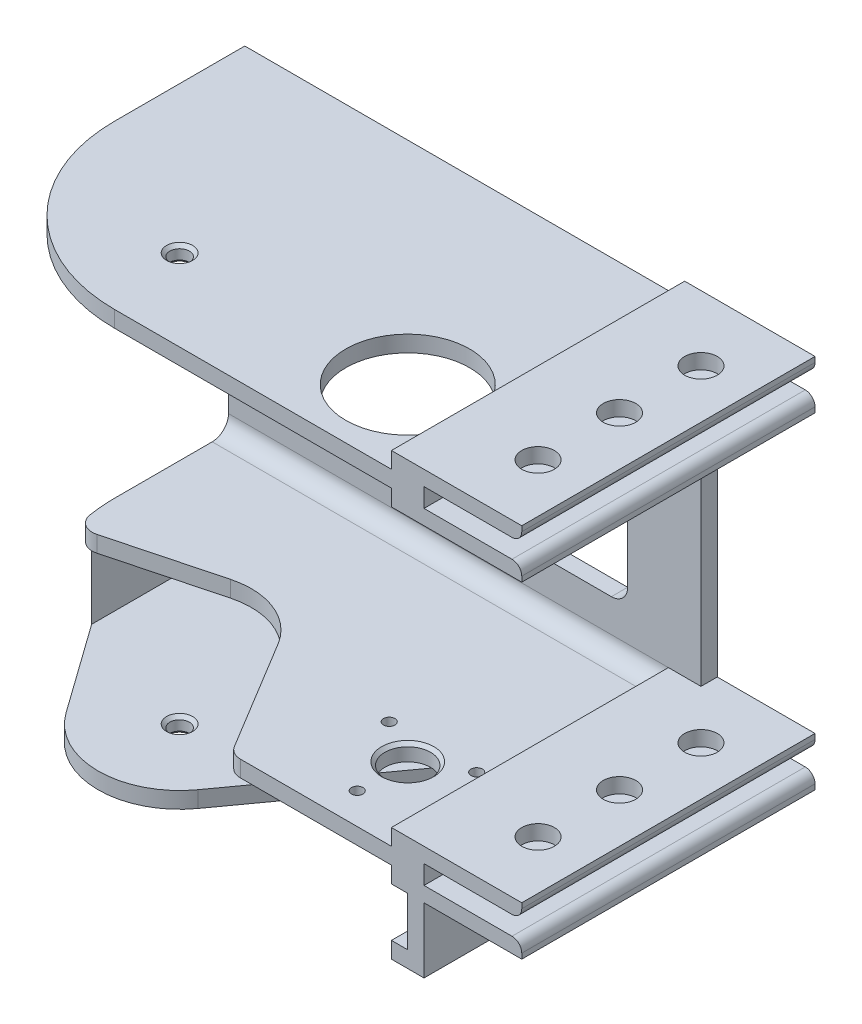
SolidWorks part; units mm, degrees
ref_plane "정면" through (0, 0, 0) normal (0, 0, 1) x (1, 0, 0)
ref_plane "윗면" through (0, 0, 0) normal (0, 1, 0) x (1, 0, 0)
ref_plane "우측면" through (0, 0, 0) normal (1, 0, 0) x (0, 0, -1)
sketch "스케치1" plane through (0, 0, 0) normal (0, 0, 1) x (1, 0, 0)
  line L0 (67.5, -47.6) -> (-67.5, -47.6)
  line L1 (-67.5, -52.6) -> (67.5, -52.6)
  line L2 (-67.5, -52.6) -> (-67.5, -72.6)
  line L3 (-67.5, -72.6) -> (67.5, -72.6)
  line L4 (67.5, -77.6) -> (-67.5, -77.6)
  line L5 (-52.5, -47.6) -> (-12.5, -47.6)
  line L6 (67.5, -57.6) -> (67.5, -72.6)
  line L7 (67.5, -47.6) -> (72.5, -47.6)
  line L8 (72.5, -47.6) -> (72.5, -52.6)
  line L9 (72.5, -57.6) -> (72.5, -77.6)
  line L10 (72.5, -77.6) -> (67.5, -77.6)
  line L11 (-67.5, -47.6) -> (-72.5, -47.6)
  line L12 (-72.5, -47.6) -> (-72.5, -77.6)
  line L13 (-72.5, -77.6) -> (-67.5, -77.6)
  line L14 (-72.5, 47.6) -> (72.5, 47.6)
  line L15 (-72.5, -47.6) -> (-72.5, 47.6)
  line L16 (72.5, -42.6) -> (72.5, 42.6)
  line L17 (72.5, 47.6) -> (72.5, 52.6)
  line L18 (72.5, 52.6) -> (-72.5, 52.6)
  line L19 (-72.5, 52.6) -> (-72.5, 47.6)
  line L20 (62.5, 42.6) -> (102.5, 42.6)
  line L21 (102.5, 42.6) -> (102.5, 47.6)
  line L22 (102.5, 47.6) -> (62.5, 47.6)
  line L23 (62.5, 47.6) -> (62.5, 42.6)
  line L24 (62.5, 52.6) -> (102.5, 52.6)
  line L25 (102.5, 52.6) -> (102.5, 57.6)
  line L26 (102.5, 57.6) -> (62.5, 57.6)
  line L27 (62.5, 57.6) -> (62.5, 52.6)
  line L28 (72.5, 0) -> (-72.5, 0) construction
  line L29 (62.5, -42.6) -> (102.5, -42.6)
  line L30 (102.5, -42.6) -> (102.5, -47.6)
  line L31 (102.5, -47.6) -> (62.5, -47.6)
  line L32 (62.5, -47.6) -> (62.5, -42.6)
  line L33 (62.5, -52.6) -> (102.5, -52.6)
  line L34 (102.5, -52.6) -> (102.5, -57.6)
  line L35 (102.5, -57.6) -> (62.5, -57.6)
  line L36 (62.5, -57.6) -> (62.5, -52.6)
  line L37 (0, 52.6) -> (0, -77.6) construction
extrude "보스-돌출1" add sketch "스케치1" against normal blind 5 contours L18 L19 L14 L17 | L0 L32 L29 L16 L20 L23 L14 L15 L11 | L9 L35 L6 L3 L2 L1 L33 L8 L7 L0 L11 L12 L13 L4 L10 | L35 L36 L1 L2 L3 L6 | L14 L23 L20 L21 L22 | L26 L27 L18 L24 L25 | L32 L0 L7 L31 L30 L29 | L36 L35 L34 L33 L1 region at (70, -49.0807, 0) region at (82.5, -45.1, 0) region at (-0.4926, 0, 0) region at (82.5, -55.1, 0) region at (82.5, 45.1, 0) region at (-0.6075, -62.6701, 0) region at (0, 50.1, 0) region at (82.5, 55.1, 0)
extrude "보스-돌출2" add sketch "스케치1<3>" along normal blind 85 contours L18 L19 L14 L17 | L9 L35 L6 L3 L2 L1 L33 L8 L7 L0 L11 L12 L13 L4 L10 | L36 L35 L34 L33 L1 | L32 L0 L7 L31 L30 L29 | L14 L23 L20 L21 L22 | L26 L27 L18 L24 L25 region at (70, -49.0807, 0) region at (82.5, -45.1, 0) region at (82.5, -55.1, 0) region at (82.5, 45.1, 0) region at (0, 50.1, 0) region at (82.5, 55.1, 0)
sketch "스케치1<3>" plane through (0, 0, 0) normal (0, 0, 1) x (1, 0, 0) same geometry as "스케치1"
sketch "스케치2" plane through (0, 0, 85) normal (0, 0, 1) x (1, 0, 0)
  line L0 (102.5, -42.6) -> (102.5, -47.6) construction
  line L1 (72.5, -53) -> (102.5, -53)
  line L2 (72.5, -53) -> (72.5, -47.2)
  line L3 (72.5, -47.2) -> (102.5, -47.2)
  line L4 (102.5, -53) -> (102.5, -47.2)
  line L5 (102.5, 52.6) -> (102.5, 57.6) construction
  line L6 (72.5, 47.2) -> (102.5, 47.2)
  line L7 (72.5, 47.2) -> (72.5, 53)
  line L8 (72.5, 53) -> (102.5, 53)
  line L9 (102.5, 47.2) -> (102.5, 53)
  line L10 (102.5, 52.6) -> (72.5, 52.6) construction
  line L11 (72.5, 47.6) -> (102.5, 47.6) construction
  line L12 (102.5, -47.6) -> (72.5, -47.6) construction
  line L13 (72.5, -52.6) -> (102.5, -52.6) construction
  line L14 (72.5, -47.6) -> (72.5, -52.6) construction
  line L15 (72.5, 47.6) -> (72.5, 52.6) construction
  dimension "D1" = 0.4
  dimension "D2" = 0.4
  dimension "D3" = 0.4
  dimension "D4" = 0.4
extrude "컷-돌출1" cut sketch "스케치2" against normal blind 130
sketch "스케치3" plane through (0, -77.6, 0) normal (0, -1, 0) x (1, 0, 0)
  line L0 (-72.5, 60) -> (72.5, 60) construction
  line L1 (-72.5, -5) -> (-72.5, 85) construction
  line L2 (72.5, -5) -> (72.5, 85) construction
  line L3 (42.5, 85) -> (42.5, -5) construction
  line L4 (-72.5, 85) -> (72.5, 85) construction
  line L5 (-72.5, -5) -> (72.5, -5) construction
  line L6 (-27.5, -5) -> (-27.5, 85) construction
  circle A0 centre (-27.5, 60) radius 3
  circle A1 centre (42.5, 60) radius 3
  dimension "D1" = 65
  dimension "D4" = 6
  dimension "D5" = 6
  dimension "D2" = 45
  dimension "D3" = 70
extrude "컷-돌출2" cut sketch "스케치3" against normal blind 188
sketch "스케치4" plane through (0, -47.6, 0) normal (0, 1, 0) x (1, 0, 0)
  circle A0 centre (-27.5, -60) radius 22
  dimension "D1" = 44
extrude "컷-돌출3" cut sketch "스케치4" against normal blind 10
sketch "스케치5" plane through (0, -77.6, 0) normal (0, -1, 0) x (1, 0, 0)
  line L0 (42.5, 60) -> (42.5, -5) construction
  line L1 (-72.5, -5) -> (72.5, -5) construction
  line L2 (42.5, 40) -> (42.5, 143.4031) construction
  line L3 (22.5, 40) -> (22.5, 143.4031)
  line L4 (62.5, 40) -> (62.5, 143.4031)
  arc A0 (22.5, 40) -> (62.5, 40) centre (42.5, 40) ccw
  arc A1 (62.5, 143.4031) -> (22.5, 143.4031) centre (42.5, 143.4031) ccw
  point P7 (42.5, 91.7016)
  dimension "D1" = 20
  dimension "D2" = 20
extrude "컷-돌출4" cut sketch "스케치5" against normal blind 10
sketch "스케치6" plane through (0, -52.6, 0) normal (0, -1, 0) x (1, 0, 0)
  circle A0 centre (42.5, 60) radius 7
  circle A1 centre (42.5, 60) radius 15.5 construction
  circle A2 centre (42.5, 75.5) radius 1.75
  circle A3 centre (55.9234, 52.25) radius 1.75
  circle A4 centre (29.0766, 52.25) radius 1.75
  point P12 (42.5, 60)
  dimension "D1" = 14
  dimension "D2" = 31
  dimension "D3" = 3.5
  dimension "D4" = 3
extrude "컷-돌출5" cut sketch "스케치6" against normal blind 10
sketch "스케치7" plane through (0, -52.6, 0) normal (0, -1, 0) x (1, 0, 0)
  circle A0 centre (42.5, 75.5) radius 3.5
  circle A1 centre (29.0766, 52.25) radius 3.5
  circle A2 centre (55.9234, 52.25) radius 3.5
  dimension "D1" = 7
extrude "컷-돌출6" cut sketch "스케치7" against normal blind 1.5
sketch "스케치8" plane through (0, -77.6, 0) normal (0, -1, 0) x (1, 0, 0)
  line L0 (-72.5, 85) -> (22.5, 85) construction
  line L1 (-7.2427, 74.6506) -> (26.2941, 28.2795)
  line L2 (-72.5, 40) -> (-47.8457, 74.5277)
  line L9 (22.5, 40) -> (22.5, 85)
  line L10 (22.5, 85) -> (-72.5, 85)
  line L11 (-72.5, 85) -> (-72.5, -5)
  line L12 (-72.5, -5) -> (72.5, -5)
  line L13 (72.5, -5) -> (72.5, 85)
  line L14 (72.5, 85) -> (62.5, 85)
  line L15 (62.5, 85) -> (62.5, 40)
  line L16 (22.5, 40) -> (22.5, 85)
  line L17 (22.5, 85) -> (-72.5, 85)
  line L18 (-72.5, 85) -> (-72.5, -5)
  line L19 (-72.5, -5) -> (72.5, -5)
  line L20 (72.5, -5) -> (72.5, 85)
  line L21 (72.5, 85) -> (62.5, 85)
  line L22 (62.5, 85) -> (62.5, 40)
  circle A0 centre (-27.5, 60) radius 25
  arc A2 (22.5, 40) -> (62.5, 40) centre (42.5, 40) ccw
  arc A3 (22.5, 40) -> (62.5, 40) centre (42.5, 40) ccw
  line M11 (22.5, 40) -> (22.5, 85)
  line M12 (22.5, 85) -> (-72.5, 85)
  line M13 (-72.5, 85) -> (-72.5, -5)
  arc M18 (62.5, 40) -> (22.5, 40) centre (42.5, 40) cw
  dimension "D1" = 0
extrude "컷-돌출7" cut sketch "스케치8" against normal up to surface (25 mm away) contours A0 L17 L2 M13 | A0 L1 M18 M11 M12 region at (9.5144, -77.6, 68.0615) region at (-61.0474, -77.6, 70.422) up to face at (42.5, -52.6, 72)
fillet "필렛2" radius 50 2 edges at (-72.5, -50.1, 85) (-72.5, 50.1, 85)
fillet "필렛3" radius 30 1 edges at (-72.2063, -65.1, 40.4113)
sketch "스케치9" plane through (0, 52.6, 0) normal (0, 1, 0) x (1, 0, 0)
  circle A0 centre (42.5, -60) radius 19
  dimension "D1" = 38
extrude "컷-돌출8" cut sketch "스케치9" against normal blind 9.5
fillet "필렛4" radius 3 4 edges at (102.5, 53, 40) (102.5, 47.2, 40) (102.5, -47.2, 40) (102.5, -53, 40)
sketch "스케치10" plane through (0, 0, 0) normal (0, 0, 1) x (1, 0, 0)
  line L0 (-72.5, -52.6) -> (-22.5, -52.6) construction
  line L1 (-50, 32.5) -> (50, 32.5)
  line L2 (-50, 32.5) -> (-50, -32.5)
  line L3 (-50, -32.5) -> (50, -32.5)
  line L4 (50, 32.5) -> (50, -32.5)
  line L5 (-50, 32.5) -> (50, -32.5) construction
  line L6 (-50, -32.5) -> (50, 32.5) construction
  line L7 (-50, -68.6) -> (50, -68.6)
  line L8 (-50, -68.6) -> (-50, -58.6)
  line L9 (-50, -58.6) -> (50, -58.6)
  line L10 (50, -68.6) -> (50, -58.6)
  line L11 (-50, -68.6) -> (50, -58.6) construction
  line L12 (-50, -58.6) -> (50, -68.6) construction
  point P0 (0, 0)
  point P6 (0, -63.6)
  dimension "D1" = 100
  dimension "D2" = 65
  dimension "D3" = 100
  dimension "D4" = 10
  dimension "D5" = 6
extrude "컷-돌출9" cut sketch "스케치10" against normal blind 9.5
sketch "스케치11" plane through (0, -47.6, 0) normal (0, 1, 0) x (1, 0, 0)
  line L0 (-33.1052, -38.726) -> (-70.6125, -48.6084)
  line L1 (-8.679, -48.6084) -> (13.3474, -85)
  line L2 (-22.5, -85) -> (62.5, -85) construction
  line L7 (-72.5, 0) -> (-72.5, -35)
  line L8 (-22.5, -85) -> (62.5, -85)
  line L9 (62.5, -85) -> (62.5, 0)
  line L10 (62.5, 0) -> (-72.5, 0)
  line L11 (-72.5, 0) -> (-72.5, -35)
  line L12 (-22.5, -85) -> (62.5, -85)
  line L13 (62.5, -85) -> (62.5, 0)
  line L14 (62.5, 0) -> (-72.5, 0)
  arc A0 (-72.5, -35) -> (-22.5, -85) centre (-22.5, -35) ccw construction
  circle A1 centre (-27.5, -60) radius 22 construction
  arc A3 (-72.5, -35) -> (-22.5, -85) centre (-22.5, -35) ccw
  arc A4 (-72.5, -35) -> (-22.5, -85) centre (-22.5, -35) ccw
  circle M12 centre (-27.5, -60) radius 22
  arc M14 (-72.5, -35) -> (-22.5, -85) centre (-22.5, -35) ccw
  line M15 (-22.5, -85) -> (62.5, -85)
  dimension "D1" = 0
extrude "컷-돌출10" cut sketch "스케치11" against normal blind 9.5 contours L1 L0 M12 M14 M15 region at (-41.5144, -47.6, 78.1851)
fillet "필렛5" radius 5 2 edges at (13.3474, -50.1, 85) (-70.6125, -50.1, 48.6084)
fillet "필렛6" radius 5 8 edges at (50, -68.6, -2.5) (50, -58.6, -2.5) (-50, -68.6, -2.5) (-50, -58.6, -2.5) (-50, -32.5, -2.5) (50, -32.5, -2.5) (50, 32.5, -2.5) (-50, 32.5, -2.5)
fillet "필렛7" radius 5 2 edges at (-5, -47.6, 0) (-5, 47.6, 0)
sketch "스케치12" plane through (0, -57.6, 0) normal (0, -1, 0) x (1, 0, 0)
  line L0 (87.5, 85) -> (87.5, -5) construction
  line L1 (102.5, 85) -> (72.5, 85) construction
  line L2 (102.5, -5) -> (72.5, -5) construction
  circle A0 centre (87.5, 65) radius 5
  circle A1 centre (87.5, 40) radius 5
  circle A2 centre (87.5, 15) radius 5
  dimension "D3" = 10
  dimension "D4" = 10
  dimension "D5" = 10
  dimension "D1" = 25
  dimension "D2" = 25
extrude "컷-돌출11" cut sketch "스케치12" against normal blind 144.5
chamfer "모따기1" distance 1 angle 45 5 edges at (-27.5, -77.6, 57) (-27.5, 52.6, 63) (-27.5, 47.6, 63) (-27.5, -72.6, 63) (42.5, -47.6, 67)
